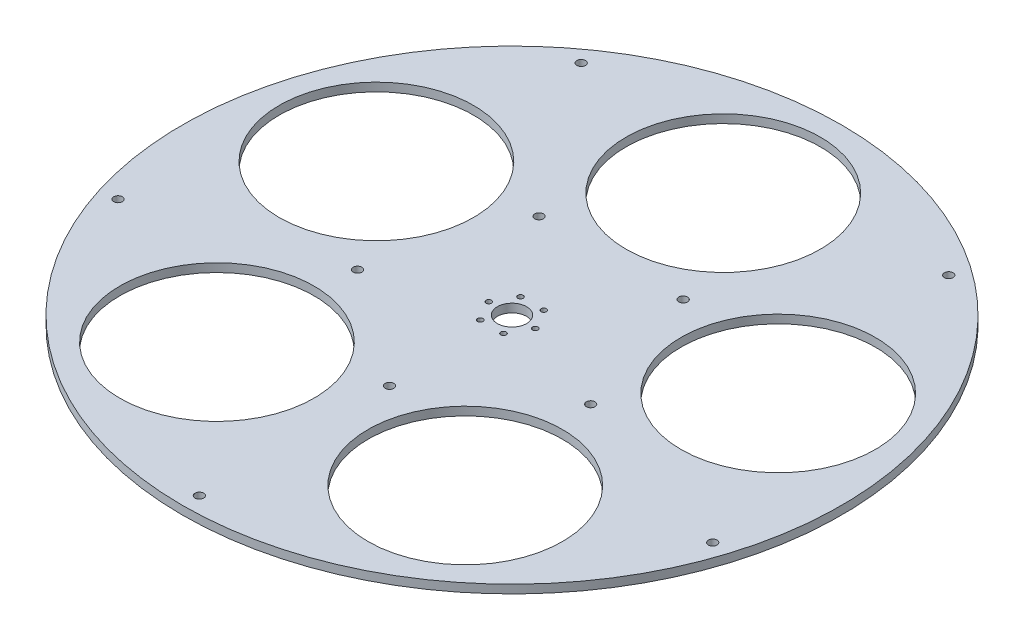
SolidWorks part; units mm, degrees
material "PC High Viscosity"
ref_plane "Front Plane" through (0, 0, 0) normal (0, 0, 1) x (1, 0, 0)
ref_plane "Top Plane" through (0, 0, 0) normal (0, 1, 0) x (1, 0, 0)
ref_plane "Right Plane" through (0, 0, 0) normal (1, 0, 0) x (0, 0, -1)
sketch "Sketch1" plane through (0, 0, 0) normal (0, 1, 0) x (1, 0, 0)
  circle A0 centre (0, 0) radius 247.65
  circle A1 centre (0, 158.75) radius 73.025
  circle A2 centre (150.9802, 49.0564) radius 73.025
  circle A3 centre (93.3109, -128.4314) radius 73.025
  circle A4 centre (-93.3109, -128.4314) radius 73.025
  circle A5 centre (-150.9802, 49.0564) radius 73.025
  point P6 (0, 247.65)
  point P7 (0, 0)
  point P15 (0, 0)
  dimension "D1" = 88.9
  dimension "D2" = 146.05
  dimension "D3" = 158.75
  dimension "D4" = 5
extrude "Boss-Extrude1" add sketch "Sketch1" along normal blind 6.35
sketch "Sketch3" plane through (-5.1845, 6.35, -2.4486) normal (0, 1, 0) x (1, 0, 0)
  circle A0 centre (5.1845, -2.4486) radius 11
  circle A1 centre (5.1845, -2.4486) radius 247.65 construction
  dimension "D1" = 22
extrude "Cut-Extrude1" cut sketch "Sketch3" against normal through all
hole_wizard "#10-32 Tapped Hole1" positions "Sketch5" profile "Sketch7" tap size "#10-32" standard "ANSI Inch" end condition through all
sketch "Sketch5" plane through (-5.1845, 6.35, -2.4486) normal (0, 1, 0) x (1, 0, 0)
  line L0 (5.1845, -2.4486) -> (-3.5467, 12.6744) construction
  line L2 (5.1845, -2.4486) -> (5.1845, 15.0139) construction
  circle A0 centre (5.1845, -2.4486) radius 17.4625
  point P0 (-3.5467, 12.6744)
  point P22 (13.9158, 12.6744)
  point P23 (22.647, -2.4486)
  point P24 (13.9158, -17.5715)
  point P25 (-3.5467, -17.5715)
  point P26 (-12.278, -2.4486)
  dimension "D1" = 34.925
  dimension "D2" = 30
  dimension "D3" = 6
sketch "Sketch7" plane through (-8.7313, 6.35, -15.123) normal (1, 0, 0) x (0, 0, 1)
  line L0 (0, 0) -> (0, 6.35)
  line L1 (0, 6.35) -> (2.0193, 6.35)
  line L2 (2.0193, 6.35) -> (2.0193, 0)
  line L5 (2.0193, 0) -> (0, 0)
  line L11 (0, -6.35) -> (0, 107.95) construction
  dimension "Thru Tap Drill Dia." = 4.0386
  dimension "Thru Tap Drill Depth" = 6.35
cosmetic thread "Hole Thread1" parameters "D2"=4.826
cosmetic thread "Hole Thread2" parameters "D2"=4.826
cosmetic thread "Hole Thread3" parameters "D2"=4.826
cosmetic thread "Hole Thread4" parameters "D2"=4.826
cosmetic thread "Hole Thread5" parameters "D2"=4.826
cosmetic thread "Hole Thread6" parameters "D2"=4.826
sketch "Sketch8" plane through (0, 6.35, 0) normal (0, 1, 0) x (1, 0, 0)
  circle A0 centre (0, -234.95) radius 3.2512
  circle A1 centre (-223.4507, -72.6035) radius 3.2512
  circle A2 centre (-138.1001, 190.0785) radius 3.2512
  circle A3 centre (138.1001, 190.0785) radius 3.2512
  circle A4 centre (223.4507, -72.6035) radius 3.2512
  circle A5 centre (0, 0) radius 247.65 construction
  point P14 (0, 0)
  dimension "D2" = 6.5024
  dimension "D1" = 234.95
  dimension "D3" = 5
extrude "Cut-Extrude2" cut sketch "Sketch8" against normal through all
sketch "Sketch9" plane through (0, 6.35, 0) normal (0, 1, 0) x (1, 0, 0)
  line L0 (0, -92.075) -> (0, 0)
  circle A0 centre (0, 0) radius 92.075 construction
  circle A1 centre (0, -92.075) radius 3.2639
  dimension "D1" = 184.15
  dimension "D2" = 6.5278
extrude "Cut-Extrude3" cut sketch "Sketch9" against normal through all contours A1
pattern_circular "CirPattern1" count 5 over 360 about axis through (0, 6.35, 0) along (0, 1, 0) of "Cut-Extrude3"
